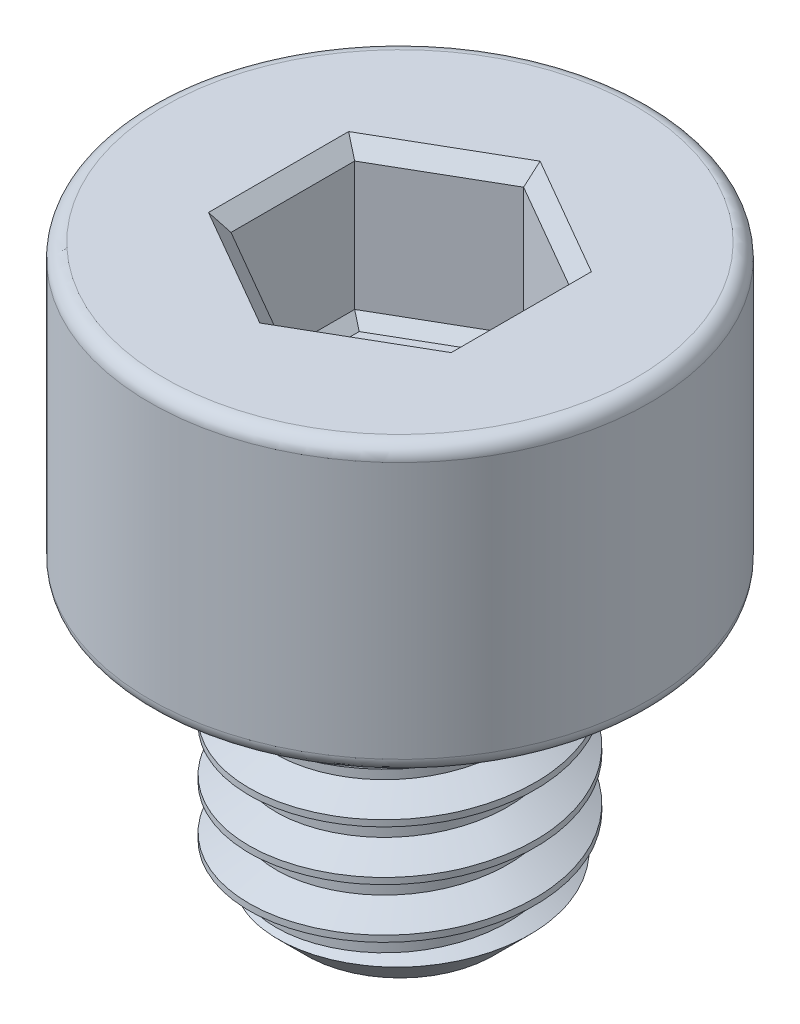
SolidWorks part; units mm, degrees
material "AISI Type A2 Tool Steel"
ref_plane "Front Plane" through (0, 0, 0) normal (0, 0, 1) x (1, 0, 0)
ref_plane "Top Plane" through (0, 0, 0) normal (0, 1, 0) x (1, 0, 0)
ref_plane "Right Plane" through (0, 0, 0) normal (1, 0, 0) x (0, 0, -1)
sketch "Sketch1" plane through (0, 0, 0) normal (0, 1, 0) x (1, 0, 0)
  circle A0 centre (0, 0) radius 2
  dimension "D1" = 4
extrude "Boss-Extrude1" add sketch "Sketch1" along normal blind 4
thread "Thread1" pitch 0.7 method cut profile "Thread Profile1" start angle 0, offset 1, length 0, pitch 0.7, diameter 4
ref_plane "Plane1" through (2, -1, 0) normal (0, 0, 1) x (1, 0, 0)
sketch "Thread Profile1" plane through (2, -1, 0) normal (0, 0, 1) x (1, 0, 0)
  line L0 (0, 0) -> (0, 0.7) construction
  line L11 (0, 0) -> (0, 0.6125)
  line L12 (0, 0.6125) -> (-0.3789, 0.3937)
  line L13 (-0.3789, 0.3937) -> (-0.3789, 0.2187)
  line L15 (-0.3789, 0.2187) -> (0, 0)
  line L17 (-0.3789, 0.3062) -> (0, 0.3062) construction
  point P2 (0, 0)
  dimension "Pitch" = 0.7
  dimension "Profile_Angle" = 60
  dimension "Profile_Land" = 0.175
  dimension "Profile_Height" = 0.3789
sketch "Sketch4" plane through (0, 4, 0) normal (0, -1, 0) x (-1, 0, 0)
  circle A0 centre (0, 0) radius 3.5
  dimension "D1" = 7
extrude "Boss-Extrude2" add sketch "Sketch4" against normal blind 4
fillet "Fillet1" radius 0.2 2 edges at (0, 4, -3.5) (0, 8, -3.5)
sketch "Sketch6" plane through (0, 0, 0) normal (0, 0, 1) x (1, 0, 0)
  line L0 (0, 0) -> (2.01, 0) construction
  line L1 (2.01, 0) -> (2.01, 0.7)
  line L2 (2.01, 0.7) -> (1.31, 0)
  line L3 (1.31, 0) -> (2.01, 0)
  line L4 (0, 0) -> (0, 0.3482) construction
  dimension "D1" = 0.7
  dimension "D2" = 45
  dimension "D3" = 2.01
revolve "Cut-Revolve1" cut sketch "Sketch6" angle 360 about L4
sketch "Sketch7" plane through (0, 8, 0) normal (0, 1, 0) x (1, 0, 0)
  line L1 (0, 1.7321) -> (-1.5, 0.866)
  line L2 (-1.5, 0.866) -> (-1.5, -0.866)
  line L3 (-1.5, -0.866) -> (0, -1.7321)
  line L4 (0, -1.7321) -> (1.5, -0.866)
  line L5 (1.5, -0.866) -> (1.5, 0.866)
  line L6 (1.5, 0.866) -> (0, 1.7321)
  circle A0 centre (0, 0) radius 1.5 construction
  dimension "D1" = 3
extrude "Cut-Extrude1" cut sketch "Sketch7" against normal blind 2
chamfer "Chamfer1" distance 0.2 angle 45 6 edges at (-1.5, 8, 0) (-0.75, 8, 1.299) (0.75, 8, 1.299) (1.5, 8, 0) (0.75, 8, -1.299) (-0.75, 8, -1.299)
sketch "Sketch8" plane through (0, 6, 0) normal (0, 1, 0) x (1, 0, 0)
  line L1 (0, 1.7321) -> (-1.5, 0.866)
  line L2 (-1.5, 0.866) -> (-1.5, -0.866)
  line L3 (-1.5, -0.866) -> (0, -1.7321)
  line L4 (0, -1.7321) -> (1.5, -0.866)
  line L5 (1.5, -0.866) -> (1.5, 0.866)
  line L6 (1.5, 0.866) -> (0, 1.7321)
  circle A0 centre (0, 0) radius 1.5 construction
extrude "Cut-Extrude2" cut sketch "Sketch8" against normal blind 0.15 draft 45
